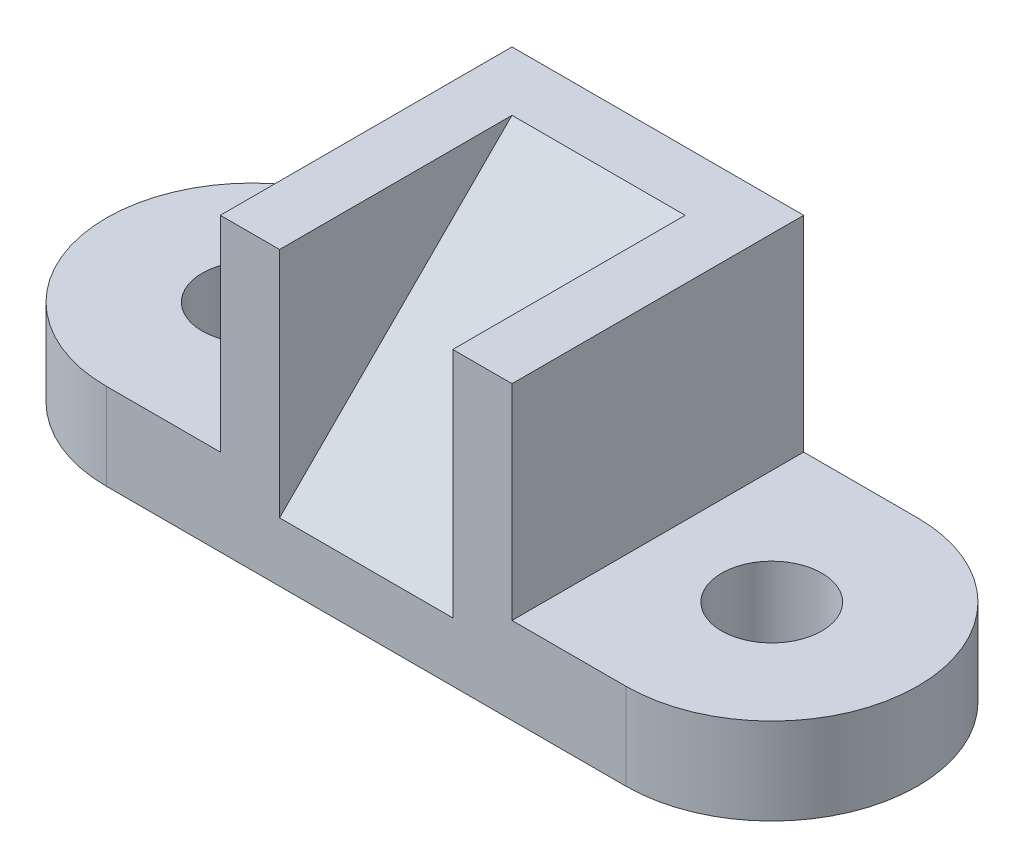
SolidWorks part; units mm, degrees
ref_plane "Front Plane" through (0, 0, 0) normal (0, 0, 1) x (1, 0, 0)
ref_plane "Top Plane" through (0, 0, 0) normal (0, 1, 0) x (1, 0, 0)
ref_plane "Right Plane" through (0, 0, 0) normal (1, 0, 0) x (0, 0, -1)
sketch "Sketch1" plane through (0, 0, 0) normal (0, 1, 0) x (1, 0, 0)
  line L0 (-57, 0) -> (57, 0) construction
  line L1 (-57, 32) -> (57, 32)
  line L2 (-57, -32) -> (57, -32)
  line L4 (-32, -32) -> (32, -32)
  line L5 (-32, -32) -> (-32, 32)
  line L6 (-32, 32) -> (32, 32)
  line L7 (32, -32) -> (32, 32)
  line L8 (-32, -32) -> (32, 32) construction
  line L9 (-32, 32) -> (32, -32) construction
  arc A0 (-57, 32) -> (-57, -32) centre (-57, 0) ccw
  arc A1 (57, -32) -> (57, 32) centre (57, 0) ccw
  circle A2 centre (-57, 0) radius 11
  circle A3 centre (57, 0) radius 11
  point P3 (0, 0)
  point P12 (0, 0)
  dimension "D2" = 22
  dimension "D3" = 32
  dimension "D1" = 114
  dimension "D4" = 64
extrude "Boss-Extrude1" add sketch "Sketch1" along normal blind 19 contours L1 A0 L2 L5 A2 | L2 A1 L1 L7 A3 region at (-44.5, 0, -31.143) region at (44.5, 0, -31.143)
extrude "Boss-Extrude2" add sketch "Sketch1<3>" along normal blind 64 contours L2 L7 L1 L5 region at (0, 0, 0)
sketch "Sketch1<3>" plane through (0, 0, 0) normal (0, 1, 0) x (1, 0, 0) same geometry as "Sketch1"
ref_plane "Plane1" through (0, 0, 0) normal (-1, 0, 0) x (0, 0, 1)
sketch "Sketch2" plane through (0, 0, 0) normal (-1, 0, 0) x (0, 0, 1)
  line L0 (32, 19) -> (32, 0) construction
  line L1 (32, 64) -> (32, 19) construction
  line L2 (32, 64) -> (-32, 64) construction
  line L3 (32, 19) -> (32, 13)
  line L4 (32, 64) -> (32, 19)
  line L5 (32, 64) -> (-19, 64)
  line L6 (-19, 64) -> (32, 13)
  line L7 (-32, 64) -> (-32, 19) construction
  line L8 (-32, 0) -> (32, 0) construction
  point P5 (32, 10.644)
  point P6 (-20.0672, 64)
  dimension "D1" = 13
  dimension "D2" = 13
extrude "Cut-Extrude1" cut sketch "Sketch2" against normal blind 19 and the other way blind 19 contours L3 L6 L5 L4
